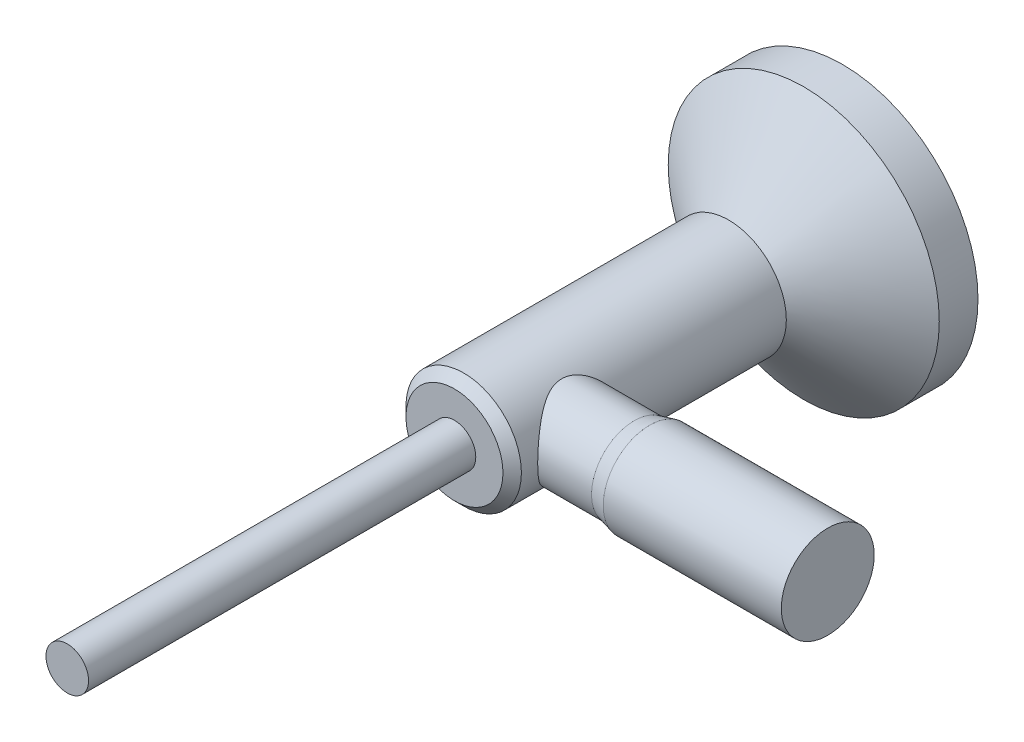
SolidWorks part; units mm, degrees
ref_plane "Plan de face" through (0, 0, 0) normal (0, 0, 1) x (1, 0, 0)
ref_plane "Plan de dessus" through (0, 0, 0) normal (0, 1, 0) x (1, 0, 0)
ref_plane "Plan de droite" through (0, 0, 0) normal (1, 0, 0) x (0, 0, -1)
sketch "Esquisse1" plane through (0, 0, 0) normal (0, 0, 1) x (1, 0, 0)
  circle A0 centre (0, 0) radius 17.5
  dimension "D1" = 35
extrude "Boss.-Extru.1" add sketch "Esquisse1" along normal blind 5
sketch "Esquisse2" plane through (0, 0, 5) normal (0, 0, 1) x (1, 0, 0)
  circle A0 centre (0, 0) radius 17.5
  dimension "D1" = 35
extrude "Boss.-Extru.2" add sketch "Esquisse2" along normal blind 9.7
chamfer "Chanfrein1" distance 9.7 distance2 13.05 1 edges at (17.5, 0, 14.7) first distance on face at (17.5, 0, 0)
sketch "Esquisse3" plane through (0, 0, 14.7) normal (0, 0, 1) x (1, 0, 0)
  circle A0 centre (0, 0) radius 7.45
  dimension "D1" = 14.9
extrude "Boss.-Extru.3" add sketch "Esquisse3" along normal blind 35.4
sketch "Esquisse4" plane through (0, 0, 50.1) normal (0, 0, 1) x (1, 0, 0)
  circle A0 centre (0, 0) radius 2.75
  dimension "D1" = 5.5
extrude "Boss.-Extru.4" add sketch "Esquisse4" along normal blind 50
sketch "Esquisse5" plane through (0, 0, 0) normal (1, 0, 0) x (0, 0, -1)
  line L0 (2.75, 0) -> (-2.75, 0) construction
  line L1 (-50.1, 7.45) -> (-50.1, -7.45) construction
  circle A0 centre (-41.3, 0) radius 5.5
  dimension "D1" = 11
  dimension "D2" = 8.8
extrude "Boss.-Extru.5" add sketch "Esquisse5" along normal blind 14.4
chamfer "Chanfrein2" distance 1.19 1 edges at (7.45, 0, 50.1)
sketch "Esquisse6" plane through (14.4, 0, 0) normal (1, 0, 0) x (0, 0, -1)
  circle A0 centre (-41.3, 0) radius 6
  dimension "D1" = 12
extrude "Boss.-Extru.6" add sketch "Esquisse6" along normal blind 25
chamfer "Chanfrein3" distance 0.5 distance2 2 1 edges at (14.4, 0, 35.3) first distance on face at (14.4, 0, 35.8)
equation "\"2mmmm\"=785.398"
